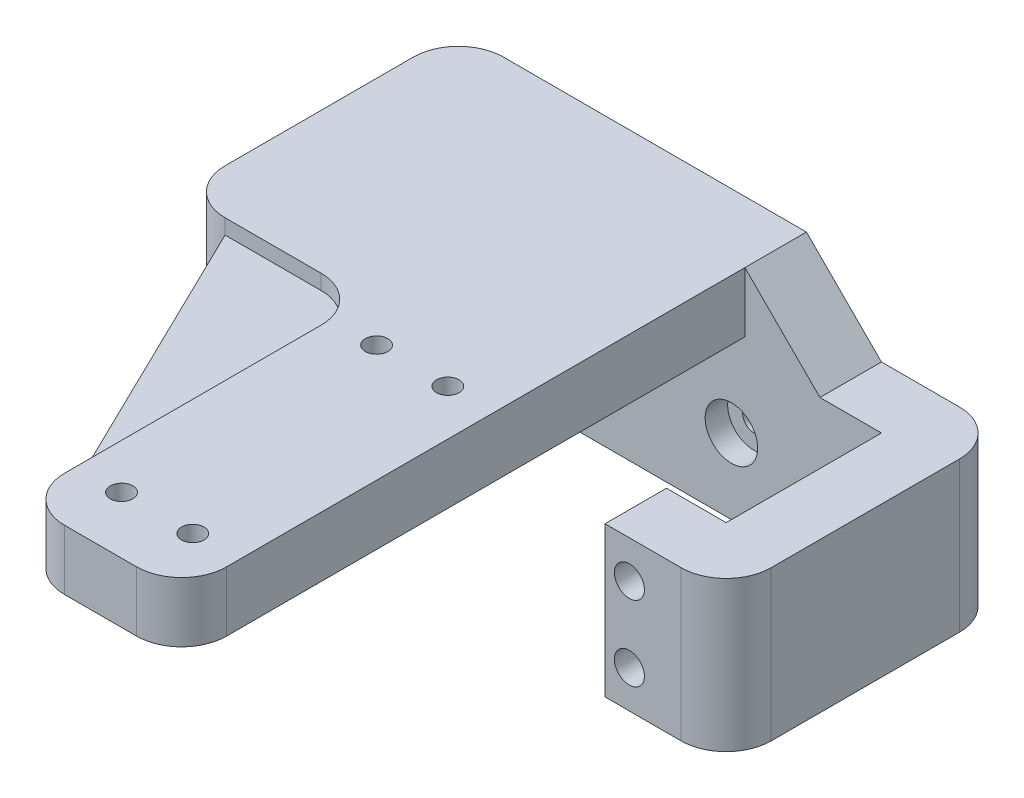
SolidWorks part; units mm, degrees
ref_plane "Piano frontale" through (0, 0, 0) normal (0, 0, 1) x (1, 0, 0)
ref_plane "Piano superiore" through (0, 0, 0) normal (0, 1, 0) x (1, 0, 0)
ref_plane "Piano destro" through (0, 0, 0) normal (1, 0, 0) x (0, 0, -1)
sketch "Schizzo1" plane through (0, 0, 0) normal (0, 0, 1) x (1, 0, 0)
  line L0 (0, 0) -> (64.6, 0)
  line L1 (64.6, 0) -> (64.6, 20)
  line L2 (64.6, 20) -> (0, 20)
  line L3 (0, 20) -> (0, 0)
  dimension "D1" = 64.6
  dimension "D2" = 20
extrude "Estrusione-Estrusione1" add sketch "Schizzo1" along normal blind 8.2
sketch "Schizzo2" plane through (0, 0, 8.2) normal (0, 0, 1) x (1, 0, 0)
  line L0 (0, 20) -> (0, 0)
  line L1 (0, 0) -> (8.2, 0)
  line L2 (0, 0) -> (64.6, 0) construction
  line L3 (8.2, 0) -> (8.2, 20)
  line L4 (64.6, 20) -> (0, 20) construction
  line L5 (8.2, 20) -> (0, 20)
  dimension "D1" = 8.2
extrude "Estrusione-Estrusione2" add sketch "Schizzo2" along normal blind 28.9
sketch "Schizzo3" plane through (0, 0, 8.2) normal (0, 0, 1) x (1, 0, 0)
  line L0 (64.6, 20) -> (64.6, 0)
  line L1 (64.6, 0) -> (56.4, 0)
  line L2 (8.2, 0) -> (64.6, 0) construction
  line L3 (56.4, 0) -> (56.4, 20)
  line L4 (64.6, 20) -> (8.2, 20) construction
  line L5 (56.4, 20) -> (64.6, 20)
  dimension "D1" = 8.2
extrude "Estrusione-Estrusione3" add sketch "Schizzo3" along normal blind 28.9
sketch "Schizzo4" plane through (56.4, 0, 0) normal (-1, 0, 0) x (0, 0, 1)
  line L0 (37.1, 20) -> (28.9, 20)
  line L1 (37.1, 20) -> (8.2, 20) construction
  line L2 (28.9, 20) -> (28.9, 0)
  line L3 (37.1, 0) -> (8.2, 0) construction
  line L4 (28.9, 0) -> (37.1, 0)
  line L5 (37.1, 0) -> (37.1, 20)
  dimension "D1" = 8.2
extrude "Estrusione-Estrusione4" add sketch "Schizzo4" along normal blind 8.2
sketch "Schizzo5" plane through (0, 0, 0) normal (-1, 0, 0) x (0, 0, 1)
  line L0 (37.1, 0) -> (0, 0)
  line L1 (0, 0) -> (0, 20)
  line L2 (0, 20) -> (37.1, 20)
  line L3 (37.1, 20) -> (37.1, 0)
extrude "Estrusione-Estrusione5" add sketch "Schizzo5" along normal blind 8.2
sketch "Schizzo6" plane through (0, 0, 0) normal (0, -1, 0) x (1, 0, 0)
  line L0 (48.2, 28.9) -> (0, 28.9)
  line L1 (0, 28.9) -> (0, 8.2)
  line L2 (0, 8.2) -> (48.2, 8.2)
  line L3 (8.2, 8.2) -> (56.4, 8.2) construction
  line L4 (48.2, 8.2) -> (48.2, 28.9)
  line L5 (8.2, 37.1) -> (8.2, 8.2) construction
  dimension "D1" = 8.2
extrude "Taglio-Estrusione1" cut sketch "Schizzo6" against normal through all
hole_wizard "Ø4.0 (4) Diameter Hole2" positions "Schizzo7" profile "Schizzo8" hole size "Ø4.0" standard "ISO" end condition up to next
sketch "Schizzo7" plane through (0, 0, 37.1) normal (0, 0, 1) x (1, 0, 0)
  line L0 (8.2, 20) -> (-8.2, 20) construction
  line L3 (64.6, 20) -> (48.2, 20) construction
  line L4 (48.2, 0) -> (48.2, 20) construction
  point P0 (51.7, 5)
  point P2 (4.7, 5)
  point P4 (4.7, 15)
  point P6 (51.7, 15)
  dimension "D1" = 10
  dimension "D2" = 10
  dimension "D3" = 47
  dimension "D4" = 47
  dimension "D5" = 5
  dimension "D6" = 0
  dimension "D7" = 3.5
  dimension "D8" = 5
sketch "Schizzo8" plane through (51.7, 5, 37.1) normal (1, 0, 0) x (0, -1, 0)
  line L0 (0, 0) -> (0, 8.2)
  line L1 (0, 8.2) -> (2, 8.2)
  line L2 (2, 8.2) -> (2, 0)
  line L5 (2, 0) -> (0, 0)
  line L11 (0, -6.35) -> (0, 107.95) construction
  dimension "Thru Hole Dia." = 4
  dimension "Thru Hole Depth" = 8.2
fillet "Raccordo3" radius 6 2 edges at (64.6, 10, 0) (64.6, 10, 37.1)
sketch "Sketch1" plane through (0, 0, 8.2) normal (0, 0, 1) x (1, 0, 0)
  line L0 (56.4, 10) -> (36.4, 10)
  line L1 (56.4, 20) -> (56.4, 0) construction
  line L2 (36.4, 10) -> (12.4, 10)
  dimension "D1" = 20
  dimension "D2" = 24
hole_wizard "CBORE for M3 Hex Head Cap Screw1" positions "Sketch2" profile "Sketch4" counterbore size "M3" standard "ISO" end condition up to next
sketch "Sketch2" plane through (0, 0, 8.2) normal (0, 0, 1) x (1, 0, 0)
  point P0 (36.4, 10)
  point P3 (12.4, 10)
sketch "Sketch4" plane through (36.4, 10, 8.2) normal (1, 0, 0) x (0, -1, 0)
  line L0 (0, 0) -> (0, 8.2)
  line L1 (0, 8.2) -> (1.5, 8.2)
  line L3 (1.5, 8.2) -> (1.5, 3)
  line L4 (1.5, 3) -> (3.5, 3)
  line L5 (3.5, 3) -> (3.5, 0)
  line L7 (3.5, 0) -> (0, 0)
  line L11 (0, -6.35) -> (0, 107.95) construction
  dimension "Thru Hole Dia." = 3
  dimension "Thru Hole Depth" = 8.2
  dimension "C'Bore Dia." = 7
  dimension "C'Bore Depth" = 3
sketch "Sketch5" plane through (0, 20, 0) normal (0, 1, 0) x (1, 0, 0)
  line L6 (38.2, -37.1) -> (-8.2, -37.1)
  line L7 (-8.2, -37.1) -> (-8.2, 0)
  line L9 (-8.2, 0) -> (38.2, 0)
  line L10 (58.6, 0) -> (-8.2, 0) construction
  line L11 (38.2, 0) -> (38.2, -37.1)
  dimension "D1" = 30
  dimension "D2" = 0
extrude "Boss-Extrude1" add sketch "Sketch5" along normal blind 10
fillet "Fillet3" radius 6 2 edges at (-8.2, 15, 0) (-8.2, 15, 37.1)
chamfer "Chamfer2" distance 10 angle 45 1 edges at (38.2, 20, 4.1)
sketch "Sketch8" plane through (0, 20, 0) normal (0, -1, 0) x (-1, 0, 0)
  line L0 (-38.2, -37.1) -> (-38.2, -8.2)
  line L1 (-38.2, -8.2) -> (0, -8.2)
  line L2 (0, -8.2) -> (0, -28.9)
  line L3 (0, -28.9) -> (-8.2, -28.9)
  line L4 (-8.2, -28.9) -> (-8.2, -37.1)
  line L5 (-8.2, -37.1) -> (-38.2, -37.1)
extrude "Cut-Extrude2" cut sketch "Sketch8" against normal blind 2
sketch "Sketch9" plane through (0, 0, 37.1) normal (0, 0, 1) x (1, 0, 0)
  line L0 (38.2, 30) -> (38.2, 22)
  line L1 (38.2, 22) -> (-2.2, 22)
  line L2 (-2.2, 30) -> (-2.2, 0) construction
  line L3 (-2.2, 22) -> (-2.2, 30)
  line L4 (-2.2, 30) -> (38.2, 30)
extrude "Boss-Extrude2" add sketch "Sketch9" along normal blind 46.2
sketch "Sketch10" plane through (0, 22, 0) normal (0, -1, 0) x (1, 0, 0)
  line L0 (22.6, 58.7) -> (-2.2, 58.7)
  line L1 (-2.2, 55.2) -> (22.6, 55.2)
  line L2 (-2.2, 83.3) -> (-2.2, 37.1) construction
  line L3 (-2.2, 58.7) -> (-2.2, 55.2)
  line L4 (-2.2, 55.2) -> (-2.2, 45.2)
  line L5 (-2.2, 45.2) -> (-2.2, 41.7)
  line L6 (-2.2, 41.7) -> (8.2, 41.7)
  line L7 (8.2, 41.7) -> (18.1, 41.7)
  line L9 (18.1, 41.7) -> (22.6, 41.7)
  line L10 (22.6, 41.7) -> (32.1, 41.7)
  line L11 (22.6, 41.7) -> (22.6, 75.7)
  line L12 (22.6, 75.7) -> (32.1, 75.7)
  dimension "D1" = 47
  dimension "D2" = 3.5
  dimension "D3" = 3.5
  dimension "D4" = 10
  dimension "D5" = 9.9
  dimension "D6" = 4.5
  dimension "D7" = 9.5
  dimension "D8" = 34
hole_wizard "CBORE for M3 Hex Head Cap Screw2" positions "Sketch11" profile "Sketch12" counterbore size "M3" standard "ISO" end condition up to next
sketch "Sketch11" plane through (0, 22, 0) normal (0, -1, 0) x (-1, 0, 0)
  point P0 (-22.6, -41.7)
  point P3 (-32.1, -41.7)
  point P7 (-22.6, -75.7)
  point P10 (-32.1, -75.7)
sketch "Sketch12" plane through (22.6, 22, 41.7) normal (1, 0, 0) x (0, 0, -1)
  line L0 (0, 0) -> (0, 8)
  line L1 (0, 8) -> (1.5, 8)
  line L3 (1.5, 8) -> (1.5, 3)
  line L4 (1.5, 3) -> (3.5, 3)
  line L5 (3.5, 3) -> (3.5, 0)
  line L7 (3.5, 0) -> (0, 0)
  line L11 (0, -6.35) -> (0, 107.95) construction
  dimension "Thru Hole Dia." = 3
  dimension "Thru Hole Depth" = 8
  dimension "C'Bore Dia." = 7
  dimension "C'Bore Depth" = 3
sketch "Sketch13" plane through (0, 22, 0) normal (0, -1, 0) x (-1, 0, 0)
  line L0 (-16.6, -83.3) -> (-16.6, -37.1)
  line L1 (2.2, -83.3) -> (-38.2, -83.3) construction
  line L2 (-16.6, -37.1) -> (2.2, -37.1)
  line L3 (2.2, -37.1) -> (2.2, -83.3)
  line L4 (2.2, -83.3) -> (-16.6, -83.3)
  line L5 (-16.6, -83.3) -> (2.2, -83.3)
  line L6 (2.2, -37.1) -> (-16.6, -75.7)
  line L7 (-16.6, -75.7) -> (-16.6, -83.3)
  dimension "D1" = 6
extrude "Cut-Extrude3" cut sketch "Sketch13" against normal through all
fillet "Fillet4" radius 6 1 edges at (38.2, 26, 83.3)
sketch "Sketch15" plane through (48.2, 0, 0) normal (-1, 0, 0) x (0, 0, 1)
  line L0 (28.9, 0) -> (28.9, 20)
  line L1 (28.9, 20) -> (37.1, 20)
  line L2 (37.1, 20) -> (37.1, 0)
  line L3 (37.1, 0) -> (28.9, 0)
extrude "Cut-Extrude4" cut sketch "Sketch15" against normal blind 0.25
sketch "Sketch16" plane through (8.2, 0, 0) normal (1, 0, 0) x (0, 0, -1)
  line L0 (-37.1, 0) -> (-37.1, 22)
  line L1 (-37.1, 22) -> (-28.9, 22)
  line L2 (-28.9, 22) -> (-28.9, 0)
  line L3 (-28.9, 0) -> (-37.1, 0)
extrude "Cut-Extrude5" cut sketch "Sketch16" against normal blind 0.25
sketch "Sketch21" plane through (0, 30, 0) normal (0, 1, 0) x (1, 0, 0)
  line L0 (-2.2, -37.1) -> (16.6, -37.1)
  line L3 (16.6, -37.1) -> (16.6, -75.7)
  line L4 (16.6, -75.7) -> (-2.2, -37.1)
extrude "Cut-Extrude6" cut sketch "Sketch21" against normal blind 2
sketch "Sketch22" plane through (0, 22, 0) normal (0, -1, 0) x (-1, 0, 0)
  line L1 (2.2, -37.1) -> (-16.6, -37.1)
  line L3 (-16.6, -37.1) -> (-16.6, -75.7)
  line L4 (-16.6, -75.7) -> (2.2, -37.1)
extrude "Cut-Extrude7" cut sketch "Sketch22" against normal blind 2
fillet "Fillet5" radius 6 1 edges at (16.6, 26, 83.3)
fillet "Fillet6" radius 6 2 edges at (16.6, 23, 37.1) (16.6, 29, 37.1)
